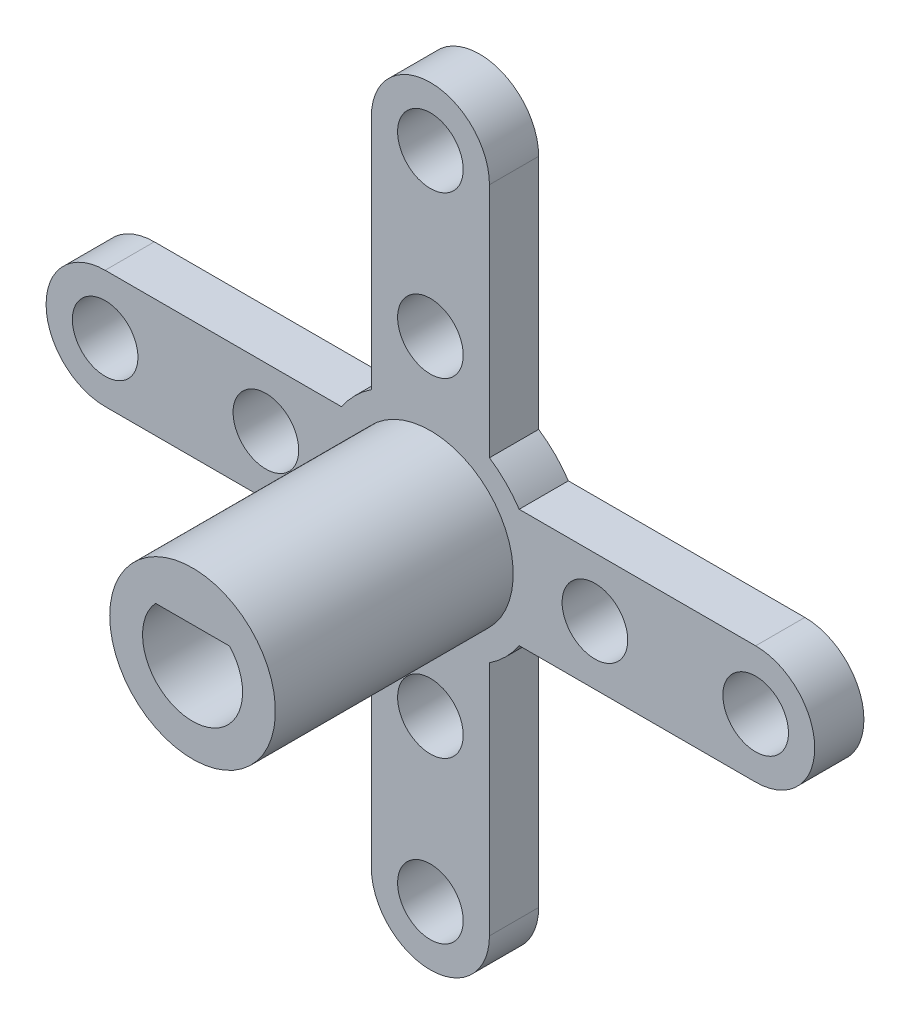
SolidWorks part; units mm, degrees
ref_plane "Přední rovina" through (0, 0, 0) normal (0, 0, 1) x (1, 0, 0)
ref_plane "Horní rovina" through (0, 0, 0) normal (0, 1, 0) x (1, 0, 0)
ref_plane "Pravá rovina" through (0, 0, 0) normal (1, 0, 0) x (0, 0, -1)
sketch "Sketch1" plane through (0, 0, 0) normal (0, 0, 1) x (1, 0, 0)
  line L0 (0, 9.915) -> (0, -9.915) construction
  line L1 (1.8, 9.915) -> (1.8, -9.915)
  line L2 (-1.8, 9.915) -> (-1.8, -9.915)
  line L3 (-9.3, 0) -> (9.3, 0) construction
  line L4 (-9.3, 1.8) -> (9.3, 1.8)
  line L5 (-9.3, -1.8) -> (9.3, -1.8)
  arc A0 (1.8, 9.915) -> (-1.8, 9.915) centre (0, 9.915) ccw
  arc A1 (-1.8, -9.915) -> (1.8, -9.915) centre (0, -9.915) ccw
  arc A2 (-9.3, 1.8) -> (-9.3, -1.8) centre (-9.3, 0) ccw
  arc A3 (9.3, -1.8) -> (9.3, 1.8) centre (9.3, 0) ccw
  circle A4 centre (0, 0) radius 1
  circle A7 centre (0, 5.015) radius 1
  circle A8 centre (0, 9.915) radius 1
  circle A9 centre (0, 0) radius 3.25
  point P3 (0, 0)
  point P10 (0, 0)
  dimension "D3" = 2
  dimension "D4" = 1.8
  dimension "D5" = 1.8
  dimension "D6" = 2
  dimension "D7" = 2
  dimension "D10" = 6.5
  dimension "D1" = 19.83
  dimension "D2" = 18.6
  dimension "D8" = 4.9
extrude "Boss-Extrude1" add sketch "Sketch1" along normal blind 1.5 contours L4 A9 L5 L2 | L5 A9 L2 | L2 A9 L1 L5 | L1 A9 L5 | L5 A9 L4 L1 | L4 A9 L1 | L1 A9 L2 L4 | L2 A9 L4 | L2 L5 L1 L4 A4 | A9 L1 A0 L2 A8 A7 | A9 region at (0, 7.1419, 0) region at (2.1218, 2.1218, 0) region at (0, 2.4476, 0) region at (2.4476, 0, 0) region at (1.7491, 0, 0) region at (-2.1218, 2.1218, 0) region at (2.1218, -2.1218, 0) region at (0, -2.4476, 0) region at (-2.4476, 0, 0) region at (-2.1218, -2.1218, 0)
pattern_circular "CirPattern1" count 4 over 360 about axis through (0, 0, 1.5) along (0, 0, 1) of "Boss-Extrude1"
sketch "Sketch2" plane through (0, 0, 0) normal (0, 0, -1) x (-1, 0, 0)
  line L1 (2.05, 1.7571) -> (-2.05, 1.7571)
  line L2 (2.05, -1.7571) -> (-2.05, -1.7571)
  circle A0 centre (0, 0) radius 2.7
  dimension "D1" = 5.4
  dimension "D2" = 4.1
  dimension "D3" = 4.1
extrude "Boss-Extrude2" [suppressed] add sketch "Sketch2" along normal blind 2
sketch "Sketch3" plane through (0, 0, 1.5) normal (0, 0, 1) x (1, 0, 0)
  line L0 (-1.1292, 1.025) -> (1.1292, 1.025)
  line L1 (0, -1.525) -> (0, 0) construction
  circle A0 centre (0, 0) radius 2.525
  circle A1 centre (0, 0) radius 1.525
  dimension "D1" = 1
  dimension "D2" = 3.05
  dimension "D3" = 2.55
extrude "Boss-Extrude3" add sketch "Sketch3" along normal blind 7.25 contours A0 A1 | L0 A1 | L0 region at (0, 1.2281, 1.5) region at (-2.4536, 0, 1.5)
